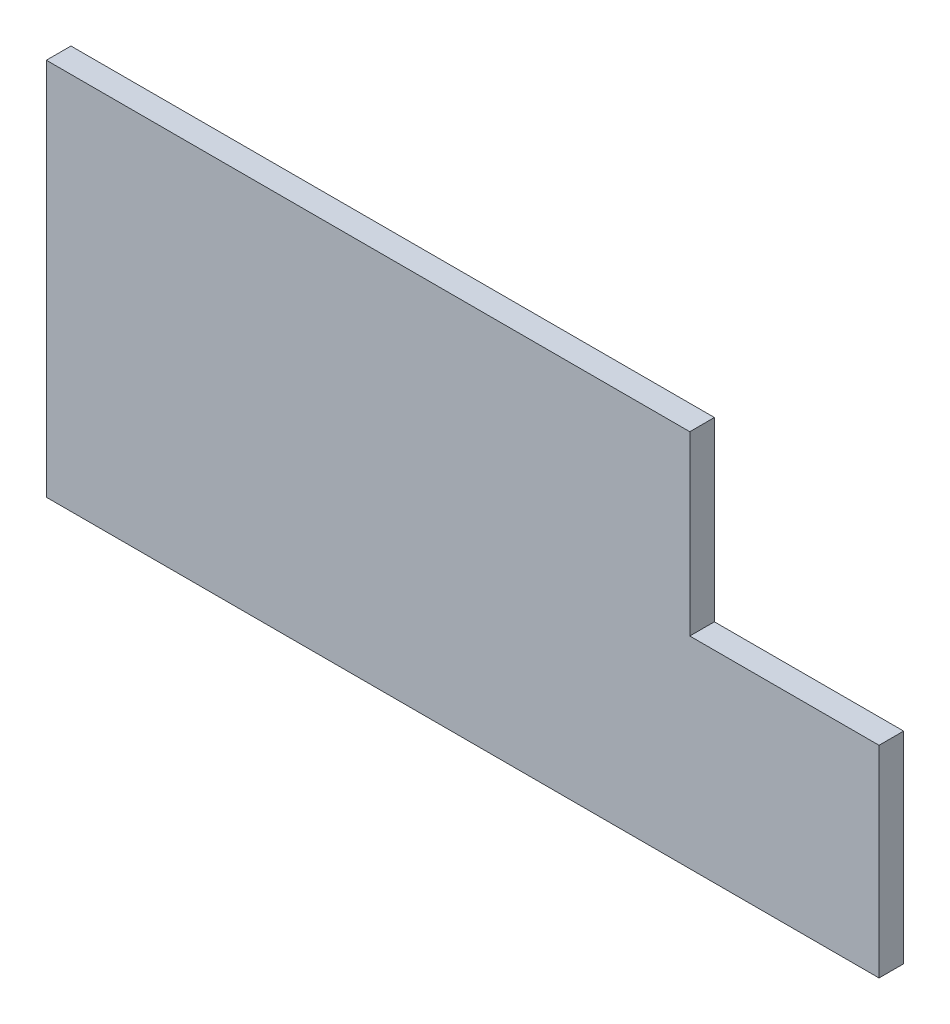
SolidWorks part; units mm, degrees
ref_plane "Plan de face" through (0, 0, 0) normal (0, 0, 1) x (1, 0, 0)
ref_plane "Plan de dessus" through (0, 0, 0) normal (0, 1, 0) x (1, 0, 0)
ref_plane "Plan de droite" through (0, 0, 0) normal (1, 0, 0) x (0, 0, -1)
sketch "Esquisse1" plane through (0, 0, 0) normal (0, 0, 1) x (1, 0, 0)
  line L1 (-103.5883, 48.6413) -> (66.4117, 48.6413)
  line L2 (-103.5883, 48.6413) -> (-103.5883, -51.3587)
  line L3 (-103.5883, -51.3587) -> (66.4117, -51.3587)
  line L4 (66.4117, 48.6413) -> (66.4117, -51.3587)
  dimension "D1" = 100
  dimension "D2" = 170
extrude "Boss.-Extru.1" add sketch "Esquisse1" along normal blind 6.5
sketch "Esquisse2" plane through (66.4117, 0, 0) normal (1, 0, 0) x (0, 0, -1)
  line L0 (0, -51.3587) -> (0, 48.6413) construction
  line L1 (-6.5, 1.8913) -> (0, 1.8913)
  line L2 (-6.5, 1.8913) -> (-6.5, -51.3587)
  line L3 (-6.5, -51.3587) -> (0, -51.3587)
  line L4 (0, 1.8913) -> (0, -51.3587)
  line L5 (-6.5, -51.3587) -> (0, -51.3587) construction
  line L6 (-6.5, -51.3587) -> (-6.5, 48.6413) construction
  dimension "D1" = 53.25
extrude "Boss.-Extru.2" add sketch "Esquisse2" along normal blind 50
